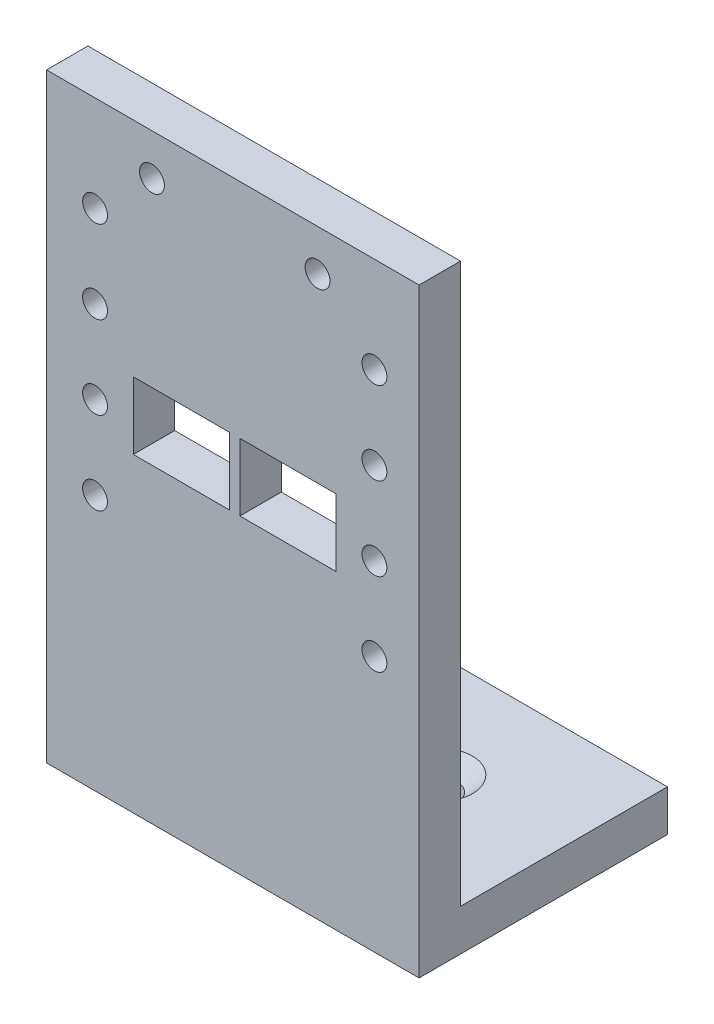
SolidWorks part; units mm, degrees
ref_plane "Płaszczyzna przednia" through (0, 0, 0) normal (0, 0, 1) x (1, 0, 0)
ref_plane "Płaszczyzna górna" through (0, 0, 0) normal (0, 1, 0) x (1, 0, 0)
ref_plane "Płaszczyzna prawa" through (0, 0, 0) normal (1, 0, 0) x (0, 0, -1)
sketch "Sketch1" plane through (0, 0, 0) normal (0, 0, 1) x (1, 0, 0)
  line L1 (-18, 29) -> (18, 29)
  line L2 (-18, 29) -> (-18, -29)
  line L3 (-18, -29) -> (18, -29)
  line L4 (18, 29) -> (18, -29)
  line L5 (-18, 29) -> (18, -29) construction
  line L6 (-18, -29) -> (18, 29) construction
  point P4 (0, 0)
  dimension "D1" = 58
  dimension "D2" = 36
extrude "Boss-Extrude1" add sketch "Sketch1" along normal blind 4
sketch "Sketch2" plane through (0, 0, 0) normal (0, 0, -1) x (-1, 0, 0)
  line L0 (-18, -29) -> (18, -29)
  line L1 (18, -29) -> (18, -25)
  line L2 (18, 29) -> (18, -29) construction
  line L3 (18, -25) -> (-18, -25)
  line L4 (-18, -29) -> (-18, 29) construction
  line L5 (-18, -25) -> (-18, -29)
  dimension "D1" = 4
extrude "Boss-Extrude2" add sketch "Sketch2" along normal blind 20 contours L3 L5 L0 L1
sketch "Sketch8" plane through (0, -25, 0) normal (0, 1, 0) x (1, 0, 0)
  line L0 (-18, 20) -> (18, 0) construction
  line L1 (-18, 0) -> (18, 20) construction
  line L2 (-18, 10) -> (18, 10) construction
  line L3 (-18, 20) -> (-18, 0) construction
  line L4 (18, 20) -> (18, 0) construction
  line L5 (-6, 20) -> (-6, 0) construction
  line L6 (-18, 20) -> (18, 20) construction
  line L7 (18, 0) -> (-18, 0) construction
  line L8 (6, 20) -> (6, 0) construction
  line L9 (-18, 20) -> (-6, 20) construction
  line L10 (-6, 20) -> (6, 20) construction
  line L11 (6, 20) -> (18, 20) construction
  point P24 (-6, 10)
  point P26 (6, 10)
hole_wizard "CSK for M3 Countersunk Flat Head Screw1" positions "Sketch8" profile "Sketch9" countersink size "M3" standard "DIN" end condition up to next
sketch "Sketch9" plane through (6, -25, -10) normal (1, 0, 0) x (0, 0, 1)
  line L0 (0, 0) -> (0, 4)
  line L1 (0, 4) -> (1.7, 4)
  line L2 (1.7, 4) -> (1.7, 1.45)
  line L3 (1.7, 1.45) -> (3.15, 0)
  line L5 (3.15, 0) -> (0, 0)
  line L6 (-1.7, 1.45) -> (-3.15, 0) construction
  line L11 (0, -6.35) -> (0, 107.95) construction
  dimension "Thru Hole Dia." = 3.4
  dimension "Thru Hole Depth" = 4
  dimension "Near C'Sink Dia." = 6.3
  dimension "Near C'Sink Angle" = 90
sketch "Sketch14" plane through (0, 0, 0) normal (0, 0, -1) x (-1, 0, 0)
  circle A0 centre (13.315, -4.2425) radius 1.25 construction
  circle A1 centre (13.315, 3.7575) radius 1.25 construction
  circle A2 centre (13.315, 11.7575) radius 1.25 construction
  circle A3 centre (13.315, 19.7575) radius 1.25 construction
  circle A4 centre (7.815, 25.0075) radius 1.25 construction
  circle A5 centre (-13.685, -4.2425) radius 1.25 construction
  circle A6 centre (-13.685, 3.7575) radius 1.25 construction
  circle A7 centre (-13.685, 11.7575) radius 1.25 construction
  circle A8 centre (-13.685, 19.7575) radius 1.25 construction
  circle A9 centre (-8.185, 25.0075) radius 1.25 construction
  circle A10 centre (13.315, -4.2425) radius 1.25
  circle A11 centre (13.315, 3.7575) radius 1.25
  circle A12 centre (13.315, 11.7575) radius 1.25
  circle A13 centre (13.315, 19.7575) radius 1.25
  circle A14 centre (7.815, 25.0075) radius 1.25
  circle A15 centre (-13.685, -4.2425) radius 1.25
  circle A16 centre (-13.685, 3.7575) radius 1.25
  circle A17 centre (-13.685, 11.7575) radius 1.25
  circle A18 centre (-13.685, 19.7575) radius 1.25
  circle A19 centre (-8.185, 25.0075) radius 1.25
hole_wizard "CSK for M2 Countersunk Flat Head Screw2" positions "Sketch15" profile "Sketch16" countersink size "M2" standard "DIN"
sketch "Sketch15" plane through (0, 0, 0) normal (0, 0, -1) x (-1, 0, 0)
  point P0 (-13.685, -4.2425)
  point P3 (-13.685, 3.7575)
  point P6 (-13.685, 11.7575)
  point P9 (-13.685, 19.7575)
  point P12 (-8.185, 25.0075)
  point P15 (7.815, 25.0075)
  point P18 (13.315, 19.7575)
  point P21 (13.315, 11.7575)
  point P24 (13.315, 3.7575)
  point P27 (13.315, -4.2425)
sketch "Sketch16" plane through (13.685, -4.2425, 0) normal (1, 0, 0) x (0, 1, 0)
  line L0 (0, 0) -> (0, 17.221)
  line L1 (0, 17.221) -> (1.2, 16.5)
  line L2 (1.2, 16.5) -> (1.2, 1)
  line L3 (1.2, 1) -> (2.2, 0)
  line L5 (2.2, 0) -> (0, 0)
  line L6 (-1.2, 1) -> (-2.2, 0) construction
  line L10 (0, 17.221) -> (-1.2, 16.5) construction
  line L11 (0, -6.35) -> (0, 107.95) construction
  dimension "Hole Dia." = 2.4
  dimension "Hole Depth" = 16.5
  dimension "Near C'Sink Dia." = 4.4
  dimension "Near C'Sink Angle" = 90
  dimension "Drill Angle" = 118
sketch "Sketch17" plane through (0, 0, 0) normal (0, 0, -1) x (-1, 0, 0)
  line L0 (9.615, 1.0075) -> (0.315, 1.0075) construction
  line L1 (0.315, 7.5075) -> (0.315, 1.0075) construction
  line L2 (9.615, 7.5075) -> (9.615, 1.0075) construction
  line L3 (0.315, 7.5075) -> (9.615, 7.5075) construction
  line L4 (-9.985, 1.0075) -> (-9.985, 7.5075) construction
  line L5 (-9.985, 7.5075) -> (-0.685, 7.5075) construction
  line L6 (-0.685, 1.0075) -> (-0.685, 7.5075) construction
  line L7 (-0.685, 1.0075) -> (-9.985, 1.0075) construction
  line L8 (9.615, 1.0075) -> (0.315, 1.0075)
  line L9 (0.315, 7.5075) -> (0.315, 1.0075)
  line L10 (9.615, 7.5075) -> (9.615, 1.0075)
  line L11 (0.315, 7.5075) -> (9.615, 7.5075)
  line L12 (-9.985, 1.0075) -> (-9.985, 7.5075)
  line L13 (-9.985, 7.5075) -> (-0.685, 7.5075)
  line L14 (-0.685, 1.0075) -> (-0.685, 7.5075)
  line L15 (-0.685, 1.0075) -> (-9.985, 1.0075)
extrude "Cut-Extrude1" cut sketch "Sketch17" against normal up to next
